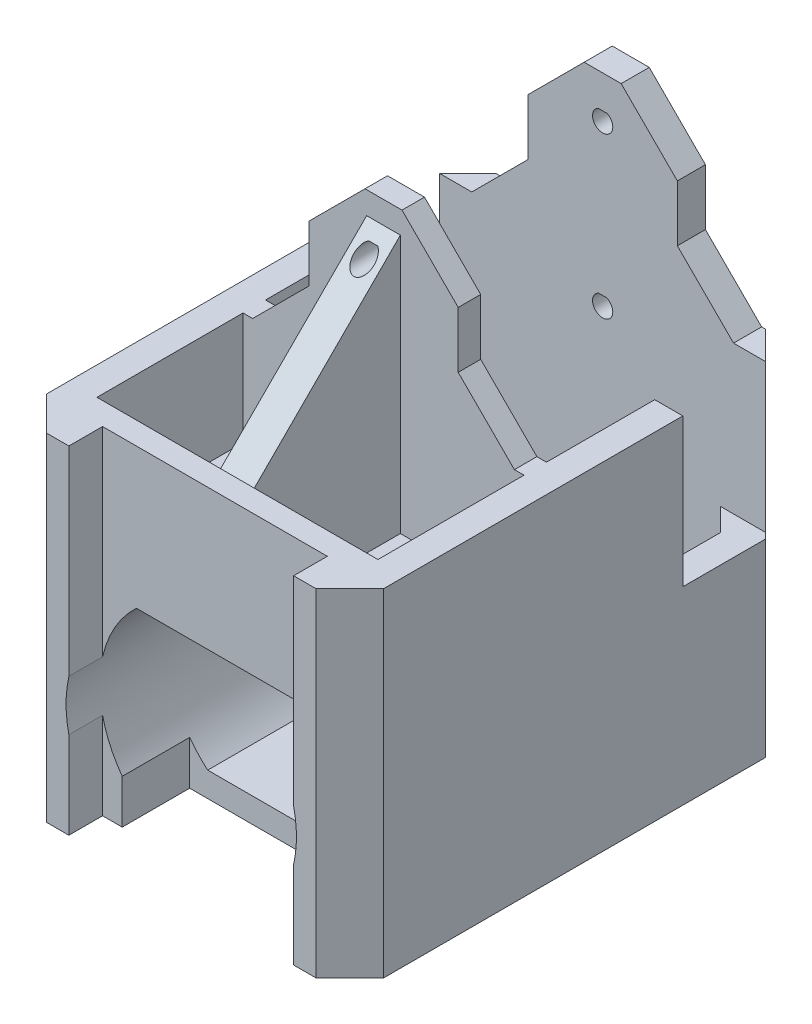
SolidWorks part; units mm, degrees
ref_plane "Front Plane" through (0, 0, 0) normal (0, 0, 1) x (1, 0, 0)
ref_plane "Top Plane" through (0, 0, 0) normal (0, 1, 0) x (1, 0, 0)
ref_plane "Right Plane" through (0, 0, 0) normal (1, 0, 0) x (0, 0, -1)
sketch "Sketch1" plane through (0, 0, 0) normal (0, 0, 1) x (1, 0, 0)
  line L1 (-15, -20) -> (15, -20)
  line L2 (-15, -20) -> (-15, 20)
  line L3 (-15, 20) -> (15, 20)
  line L4 (15, -20) -> (15, 20)
  line L5 (-15, -20) -> (15, 20) construction
  line L6 (-15, 20) -> (15, -20) construction
  point P0 (0, 0)
  dimension "D1" = 30
  dimension "D2" = 40
extrude "Boss-Extrude1" add sketch "Sketch1" along normal blind 40
sketch "Sketch2" plane through (0, 0, 40) normal (0, 0, 1) x (1, 0, 0)
  line L5 (-6.9866, -2.5) -> (6.9866, -2.5)
  line L7 (-6.6464, -17.803) -> (6.6464, -17.803)
  arc A4 (-6.9866, -2.5) -> (-6.6464, -17.803) centre (0, -10) ccw
  arc A5 (6.6464, -17.803) -> (6.9866, -2.5) centre (0, -10) ccw
  point P0 (0, -10)
  dimension "D2" = 20.5
extrude "Cut-Extrude1" cut sketch "Sketch2" against normal blind 35
sketch "Sketch4" plane through (0, 20, 0) normal (0, 1, 0) x (1, 0, 0)
  line L1 (-12.5, -37.5) -> (12.5, -37.5)
  line L2 (-12.5, -37.5) -> (-12.5, -2.5)
  line L3 (-12.5, -2.5) -> (12.5, -2.5)
  line L4 (12.5, -37.5) -> (12.5, -2.5)
  point P0 (0, -20)
  dimension "D1" = 25
  dimension "D2" = 35
extrude "Cut-Extrude3" cut sketch "Sketch4" against normal blind 20
sketch "Sketch5" plane through (0, 0, 0) normal (0, 1, 0) x (1, 0, 0)
  line L0 (12.5, -37.5) -> (12.5, -2.5) construction
  line L1 (-12.5, -2.5) -> (12.5, -2.5)
  line L2 (-12.5, -2.5) -> (-12.5, -20)
  line L3 (-12.5, -20) -> (12.5, -20)
  line L4 (12.5, -2.5) -> (12.5, -20)
extrude "Cut-Extrude4" cut sketch "Sketch5" against normal blind 20
sketch "Sketch13" plane through (0, 0, 0) normal (0, 1, 0) x (1, 0, 0)
  line L0 (12.5, -37.5) -> (12.5, -20) construction
  line L1 (-12.5, -20) -> (12.5, -20)
  line L2 (-12.5, -20) -> (-12.5, -22.0007)
  line L3 (-12.5, -22.0007) -> (12.5, -22.0007)
  line L4 (12.5, -20) -> (12.5, -22.0007)
extrude "Boss-Extrude3" add sketch "Sketch13" along normal up to surface (20 mm away) up to face at (0, 20, 20)
sketch "Sketch8" plane through (0, 0, 40) normal (0, 0, 1) x (1, 0, 0)
  line L0 (-0.5467, -9.1627) -> (0.5467, -9.1627)
  arc A3 (-0.5467, -9.1627) -> (0.5467, -9.1627) centre (0, -10.2278) ccw
extrude "Cut-Extrude5" cut sketch "Sketch8" against normal up to surface (40 mm away) up to face at (0, 0, 0)
sketch "Sketch9" plane through (0, 0, 0) normal (0, 0, -1) x (-1, 0, 0)
  line L6 (-0.3543, 7.8496) -> (0.3543, 7.8496)
  arc A2 (-0.3543, 7.8496) -> (0.3543, 7.8496) centre (0, 7.0222) ccw
extrude "Cut-Extrude6" cut sketch "Sketch9" against normal up to surface (40 mm away) up to face at (0, -10.1897, 40)
sketch "Sketch10" plane through (0, 0, 40) normal (0, 0, 1) x (1, 0, 0)
  line L0 (15, -20) -> (15, 20) construction
  line L1 (-15, 20) -> (15, 20)
  line L2 (-15, 20) -> (-15, 10)
  line L3 (-15, 10) -> (15, 10)
  line L4 (15, 20) -> (15, 10)
  dimension "D1" = 10
extrude "Cut-Extrude9" cut sketch "Sketch10" against normal up to surface (40 mm away) up to face at (0, 6.9859, 0)
chamfer "Chamfer2" distance 3 angle 45 4 edges at (15, -5, 0) (15, -5, 40) (-15, -5, 40) (-15, -5, 0)
sketch "Sketch16" plane through (-12.5, 0, 0) normal (1, 0, 0) x (0, 0, -1)
  line L1 (-2.5, 10) -> (-9.5368, 10)
  line L2 (-2.5, 10) -> (-2.5, -3.1649)
  line L6 (-9.5368, -3.1649) -> (-2.5, -3.1649)
  line L7 (-9.5368, -3.1649) -> (-10.3664, -3.1649)
  line L8 (-10.3664, -3.1649) -> (-10.3664, 10)
  line L9 (-3, 10) -> (-37, 10) construction
  line L10 (-10.3664, 10) -> (-9.5368, 10)
extrude "Cut-Extrude10" cut sketch "Sketch16" against normal mid plane 57
sketch "Sketch17" plane through (0, 10, 0) normal (0, 1, 0) x (1, 0, 0)
  line L0 (12.5, -37.5) -> (12.5, -22.0007) construction
  line L1 (-12.5, -37.5) -> (12.5, -37.5)
  line L2 (-12.5, -37.5) -> (-12.5, -35)
  line L3 (-12.5, -35) -> (12.5, -35)
  line L4 (12.5, -37.5) -> (12.5, -35)
  dimension "D1" = 2.5
extrude "Boss-Extrude4" add sketch "Sketch17" against normal up to surface (10 mm away) up to face at (0, 0, 29.7504)
sketch "Sketch18" plane through (0, 10, 0) normal (0, 1, 0) x (1, 0, 0)
  line L0 (-10, -40) -> (10, -40)
  line L1 (-12, -40) -> (12, -40) construction
  line L5 (-10, -40) -> (10, -40)
  line L6 (-10, -40) -> (-10, -37)
  line L7 (-10, -37) -> (10, -37)
  line L8 (10, -40) -> (10, -37)
  point P5 (0, -40)
  line M15 (-12, -40) -> (12, -40)
  dimension "D1" = 20
  dimension "D2" = 3
extrude "Cut-Extrude13" cut sketch "Sketch18" against normal up to surface (30 mm away) contours L8 L7 L6 M15 region at (0, 10, 38.5) up to face at (0, -20, 11.25)
sketch "Sketch19" plane through (0, -20, 0) normal (0, -1, 0) x (1, 0, 0)
  line L0 (-8.25, 37) -> (8.25, 37)
  line L1 (10, 37) -> (-10, 37) construction
  line L5 (-8.25, 37) -> (8.25, 37)
  line L6 (-8.25, 37) -> (-8.25, 31)
  line L7 (-8.25, 31) -> (8.25, 31)
  line L8 (8.25, 37) -> (8.25, 31)
  point P5 (0, 37)
  line M18 (10, 37) -> (-10, 37)
  dimension "D1" = 16.5
  dimension "D2" = 6
extrude "Cut-Extrude14" cut sketch "Sketch19" against normal blind 10 contours L8 L6 L7 M18 region at (0, -20, 34)
sketch "Sketch20" plane through (0, 0, 20) normal (0, 0, -1) x (-1, 0, 0)
  line L0 (10.25, -10) -> (12.5, -10)
  line L1 (-12.5, -10) -> (-10.25, -10)
  line L2 (-12.5, -10) -> (-12.5, -20)
  line L3 (-12.5, -20) -> (12.5, -20)
  line L4 (12.5, -20) -> (12.5, 10)
  line L5 (12.5, 10) -> (-12.5, 10)
  line L6 (-12.5, 10) -> (-12.5, -20)
  line L7 (-12.5, -20) -> (12.5, -20)
  line L8 (12.5, -20) -> (12.5, -10)
  line L10 (-12.5, -10) -> (-12.5, -20)
  line L11 (-12.5, -20) -> (12.5, -20)
  line L12 (12.5, -10) -> (12.5, -20)
  line L13 (-6.6464, -17.803) -> (6.6464, -17.803)
  arc A0 (6.6464, -17.803) -> (6.9866, -2.5) centre (0, -10) ccw construction
  arc A1 (6.6464, -17.803) -> (10.25, -10) centre (0, -10) ccw
  arc A2 (-6.9866, -2.5) -> (-6.6464, -17.803) centre (0, -10) ccw construction
  arc A3 (-10.25, -10) -> (-6.6464, -17.803) centre (0, -10) ccw
  line M7 (12.5, -20) -> (12.5, 10)
  line M9 (-12.5, 10) -> (-12.5, -20)
  line M10 (-12.5, -20) -> (12.5, -20)
  line M11 (6.6464, -17.803) -> (-6.6464, -17.803)
  arc M12 (-6.6464, -17.803) -> (-6.9866, -2.5) centre (0, -10) cw
  arc M14 (6.9866, -2.5) -> (6.6464, -17.803) centre (0, -10) cw
  dimension "D1" = 0
extrude "Boss-Extrude5" add sketch "Sketch20" along normal blind 8.5 contours L1 L0 M9 M10 M7 M14 M11 M12 region at (-11.375, -10.2693, 20)
sketch "Sketch22" plane through (0, 0, 11.5) normal (0, 0, -1) x (-1, 0, 0)
  line L0 (12.5, -20) -> (12.5, -10) construction
  line L1 (-12.5, -20) -> (12.5, -20)
  line L2 (-12.5, -20) -> (-12.5, -15)
  line L3 (-12.5, -15) -> (12.5, -15)
  line L4 (12.5, -20) -> (12.5, -15)
extrude "Boss-Extrude6" add sketch "Sketch22" along normal blind 1
sketch "Sketch23" plane through (0, 10, 0) normal (0, 1, 0) x (1, 0, 0)
  line L0 (-12.5, -10.5) -> (12.5, -10.5) construction
  line L3 (-6.6464, -22.0007) -> (6.6464, -22.0007)
  line L4 (6.6464, 0) -> (6.6464, -2.5)
  line L5 (-6.6464, 0) -> (-6.6464, -2.5)
  line L6 (-6.6464, -2.5) -> (0, -2.5)
  line L7 (-12.5, -22.0007) -> (12.5, -22.0007) construction
  line L8 (12.5, -22.0007) -> (-12.5, -22.0007) construction
  line L9 (-6.6464, -20) -> (6.6464, -20)
  line L10 (-12.5, -20) -> (12.5, -20) construction
  line L11 (-6.6464, 0) -> (6.6464, 0)
  line L12 (-12, 0) -> (12, 0) construction
  line L14 (14.5, -2.5) -> (-14.5, -2.5) construction
  line L15 (0, -2.5) -> (6.6464, -2.5)
  line L17 (-6.6464, -20) -> (-6.6464, -22.0007)
  line L18 (6.6464, -20) -> (6.6464, -22.0007)
  point P0 (0, -10.5)
  point P16 (0, -20)
  point P21 (0, 0)
extrude "Boss-Extrude7" add sketch "Sketch23" along normal blind 15
chamfer "Chamfer4" distance 5 angle 45 4 edges at (-6.6464, 10, 21.0004) (-6.6464, 10, 1.25) (6.6464, 10, 21.0004) (6.6464, 10, 1.25)
chamfer "Chamfer6" distance 5 angle 45 4 edges at (-6.6464, 25, 1.25) (-6.6464, 25, 21.0004) (6.6464, 25, 1.25) (6.6464, 25, 21.0004)
sketch "Sketch30" plane through (0, 0, 0) normal (0, 1, 0) x (1, 0, 0)
  line L3 (-12.5, -22.0007) -> (12.5, -22.0007) construction
  line L4 (-1.5, -35) -> (1.5, -35)
  line L5 (-1.5, -35) -> (-1.5, -22.0007)
  line L6 (-1.5, -22.0007) -> (1.5, -22.0007)
  line L7 (1.5, -35) -> (1.5, -22.0007)
  point P6 (0, -28.5004)
  dimension "D1" = 3
extrude "Boss-Extrude8" add sketch "Sketch30" along normal blind 24
chamfer "Chamfer10" distance 14 1 edges at (0, 24, 35)
sketch "Sketch29" plane through (0, 0, 0) normal (0, 0, -1) x (-1, 0, 0)
  line L2 (-0.4034, 22.0767) -> (0.4034, 22.0767)
  arc A1 (-0.4034, 22.0767) -> (0.4034, 22.0767) centre (0, 21.2722) ccw
extrude "Cut-Extrude15" cut sketch "Sketch29" against normal up to surface (22.9233 mm away) up to face at (0, 16.4996, 28.5004)
chamfer "Chamfer11" distance 2 angle 45 2 edges at (12.5, -11.5824, 2.5) (-12.5, -11.5824, 2.5)
